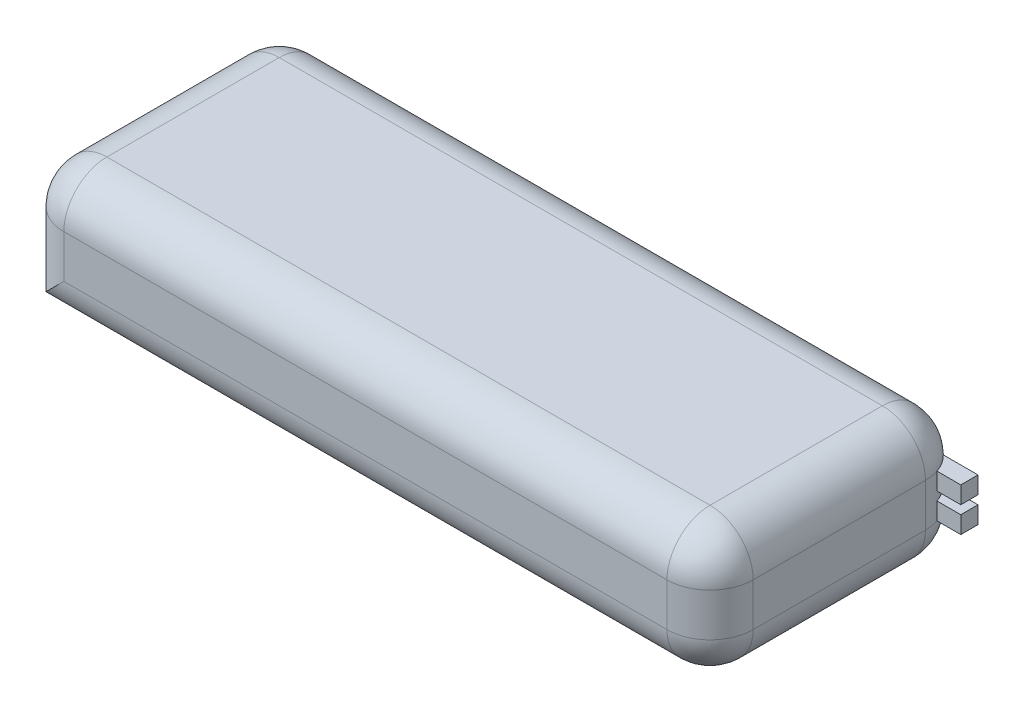
SolidWorks part; units mm, degrees
ref_plane "Front Plane" through (0, 0, 0) normal (0, 0, 1) x (1, 0, 0)
ref_plane "Top Plane" through (0, 0, 0) normal (0, 1, 0) x (1, 0, 0)
ref_plane "Right Plane" through (0, 0, 0) normal (1, 0, 0) x (0, 0, -1)
sketch "Esquisse1" plane through (0, 0, 0) normal (0, 1, 0) x (1, 0, 0)
  line L1 (-80, -30) -> (80, -30)
  line L2 (-80, -30) -> (-80, 30)
  line L3 (-80, 30) -> (80, 30)
  line L4 (80, -30) -> (80, 30)
  line L5 (-80, -30) -> (80, 30) construction
  line L6 (-80, 30) -> (80, -30) construction
  point P0 (0, 0)
  dimension "D1" = 160
  dimension "D2" = 60
extrude "Boss.-Extru.1" add sketch "Esquisse1" along normal blind 30
sketch "Esquisse2" plane through (80, 0, 0) normal (1, 0, 0) x (0, 0, -1)
  line L0 (30, 15) -> (-30, 15) construction
  line L1 (30, 30) -> (30, 0) construction
  line L2 (-30, 30) -> (-30, 0) construction
  line L3 (25.1923, 30) -> (25.1923, 0) construction
  line L4 (-30, 30) -> (30, 30) construction
  line L5 (-30, 0) -> (30, 0) construction
  line L7 (23.1923, 20) -> (27.1923, 20)
  line L8 (23.1923, 20) -> (23.1923, 16)
  line L9 (23.1923, 16) -> (27.1923, 16)
  line L10 (27.1923, 20) -> (27.1923, 16)
  line L11 (23.1923, 20) -> (27.1923, 16) construction
  line L12 (23.1923, 16) -> (27.1923, 20) construction
  line L13 (23.1923, 10) -> (27.1923, 10)
  line L14 (23.1923, 10) -> (23.1923, 14)
  line L15 (23.1923, 14) -> (27.1923, 14)
  line L16 (27.1923, 10) -> (27.1923, 14)
  line L17 (23.1923, 10) -> (27.1923, 14) construction
  line L18 (23.1923, 14) -> (27.1923, 10) construction
  point P12 (25.1923, 18)
  point P17 (25.1923, 12)
  dimension "D1" = 4
  dimension "D2" = 4
  dimension "D3" = 4
  dimension "D4" = 4
  dimension "D5" = 1
  dimension "D6" = 1
extrude "Boss.-Extru.2" add sketch "Esquisse2" along normal blind 5
fillet "Congé1" radius 10 11 edges at (-80, 15, 30) (-80, 15, -30) (0, 0, -30) (80, 15, -30) (80, 0, 0) (80, 30, 0) (-80, 30, 0) (0, 30, -30) (80, 15, 30) (0, 0, 30) (0, 30, 30)
